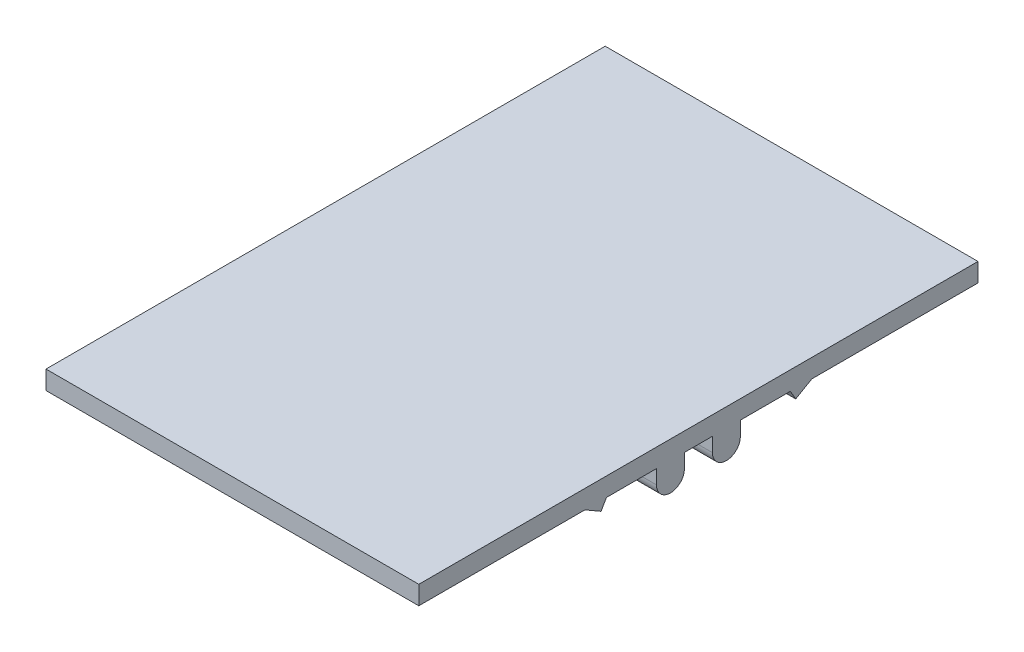
SolidWorks part; units mm, degrees
ref_plane "Front Plane" through (0, 0, 0) normal (0, 0, 1) x (1, 0, 0)
ref_plane "Top Plane" through (0, 0, 0) normal (0, 1, 0) x (1, 0, 0)
ref_plane "Right Plane" through (0, 0, 0) normal (1, 0, 0) x (0, 0, -1)
sketch "Sketch1" plane through (0, 0, 0) normal (0, 1, 0) x (1, 0, 0)
  line L1 (-200, -300) -> (200, -300)
  line L2 (-200, -300) -> (-200, 300)
  line L3 (-200, 300) -> (200, 300)
  line L4 (200, -300) -> (200, 300)
  line L5 (-200, -300) -> (200, 300) construction
  line L6 (-200, 300) -> (200, -300) construction
  point P0 (0, 0)
  dimension "D1" = 600
  dimension "D2" = 400
extrude "Boss-Extrude1" add sketch "Sketch1" along normal blind 20
sketch "Sketch3" plane through (200, 0, 0) normal (1, 0, 0) x (0, 0, -1)
  line L0 (-300, 0) -> (-30, 0) construction
  line L1 (-300, 0) -> (300, 0) construction
  line L2 (-30, 0) -> (-30, -15.1461) construction
  line L3 (-45, -15.1461) -> (-45, 0)
  line L4 (-45, 0) -> (-15, 0)
  line L5 (-15, 0) -> (-15, -15.1461)
  arc A0 (-45, -15.1461) -> (-15, -15.1461) centre (-30, -15.1461) ccw
  point P5 (0, 0)
  dimension "D2" = 15.1461
  dimension "D3" = 15
  dimension "D1" = 270
extrude "Boss-Extrude2" add sketch "Sketch3" against normal blind 30
mirror "Mirror1" about plane through (0, 0, 0) normal (0, 0, 1) of "Boss-Extrude2"
mirror "Mirror2" about plane through (0, 0, 0) normal (1, 0, 0) of "Mirror1", "Boss-Extrude2"
sketch "Sketch4" plane through (200, 0, 0) normal (1, 0, 0) x (0, 0, -1)
  line L0 (-121.7605, 0) -> (-104.44, -10)
  line L1 (-300, 0) -> (-45, 0) construction
  line L2 (-104.44, -10) -> (-98.6665, 0)
  line L3 (-98.6665, 0) -> (-121.7605, 0)
  line L4 (-113.1003, -5) -> (-134.6227, -42.278) construction
  line L5 (-130.2926, -44.778) -> (-138.9528, -39.778) construction
  dimension "D1" = 20
extrude "Boss-Extrude3" add sketch "Sketch4" against normal blind 40
mirror "Mirror3" about plane through (0, 0, 0) normal (0, 0, 1) of "Boss-Extrude3"
mirror "Mirror4" about plane through (0, 0, 0) normal (1, 0, 0) of "Boss-Extrude3", "Mirror3"
